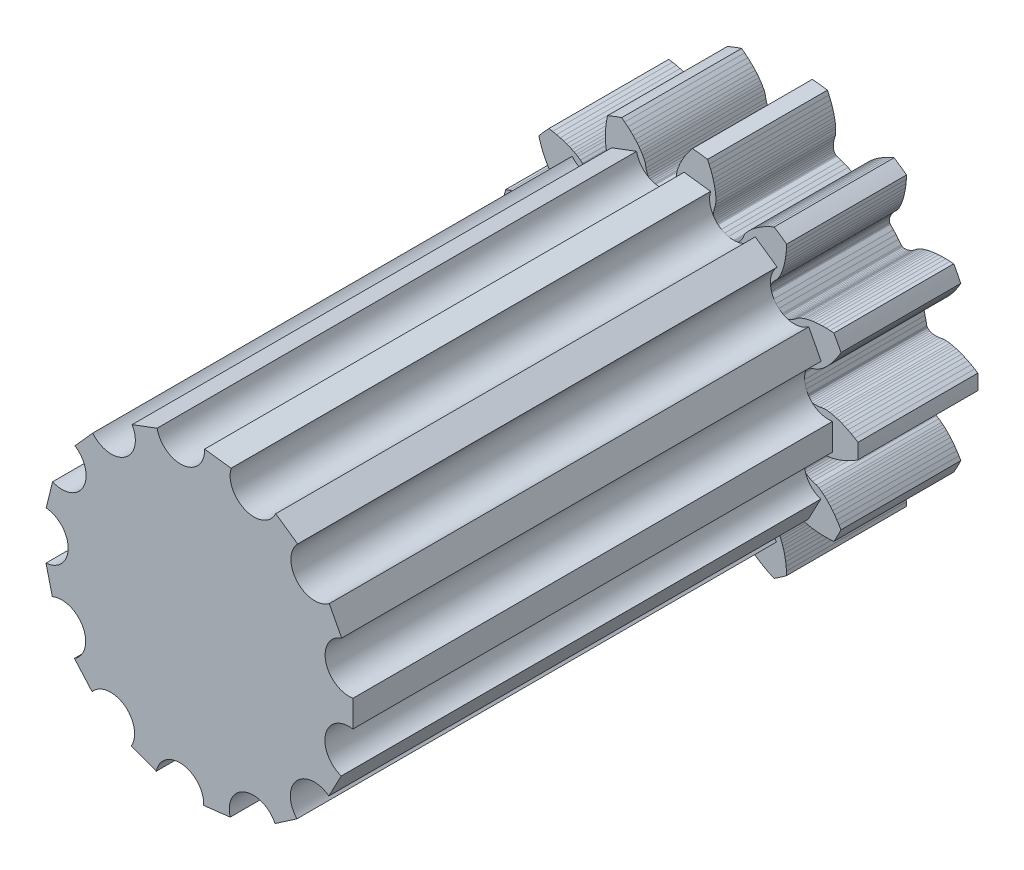
SolidWorks part; units mm, degrees
ref_plane "Front Plane" through (0, 0, 0) normal (0, 0, 1) x (1, 0, 0)
ref_plane "Top Plane" through (0, 0, 0) normal (0, 1, 0) x (1, 0, 0)
ref_plane "Right Plane" through (0, 0, 0) normal (1, 0, 0) x (0, 0, -1)
sketch "Model" plane through (0, 0, 0) normal (0, 0, 1) x (1, 0, 0)
  line L0 (13.726, -4.5793) -> (13.7795, -4.4216)
  line L1 (13.7795, -4.4216) -> (13.8362, -4.2751)
  line L2 (13.8362, -4.2751) -> (13.8946, -4.1409)
  line L3 (13.8946, -4.1409) -> (13.9531, -4.0207)
  line L4 (13.9531, -4.0207) -> (14.0126, -3.9103)
  line L5 (14.0126, -3.9103) -> (14.071, -3.8121)
  line L6 (14.071, -3.8121) -> (14.1274, -3.7258)
  line L7 (14.1274, -3.7258) -> (14.1809, -3.6508)
  line L8 (14.1809, -3.6508) -> (14.2315, -3.5859)
  line L9 (14.2315, -3.5859) -> (14.3187, -3.4872)
  line L10 (14.3187, -3.4872) -> (14.4038, -3.4082)
  line L11 (14.4038, -3.4082) -> (14.5511, -3.3203)
  line L12 (14.5511, -3.3203) -> (14.636, -3.2587)
  line L13 (14.636, -3.2587) -> (14.7072, -3.1963)
  line L14 (14.7072, -3.1963) -> (14.7648, -3.1341)
  line L15 (14.7648, -3.1341) -> (14.8089, -3.0731)
  line L16 (14.8089, -3.0731) -> (14.8397, -3.0144)
  line L17 (14.8397, -3.0144) -> (14.8576, -2.9589)
  line L18 (14.8576, -2.9589) -> (14.8629, -2.9077)
  line L19 (14.8629, -2.9077) -> (14.8609, -2.884)
  line L20 (14.8609, -2.884) -> (14.8559, -2.8617)
  line L21 (14.8559, -2.8617) -> (14.8429, -2.8311)
  line L22 (14.8429, -2.8311) -> (14.7494, -2.6711)
  line L23 (14.7494, -2.6711) -> (14.6743, -2.5327)
  line L24 (14.6743, -2.5327) -> (14.6031, -2.3923)
  line L25 (14.6031, -2.3923) -> (14.5246, -2.2245)
  line L26 (14.5246, -2.2245) -> (14.5068, -2.1964)
  line L27 (14.5068, -2.1964) -> (14.4912, -2.1796)
  line L28 (14.4912, -2.1796) -> (14.4728, -2.1645)
  line L29 (14.4728, -2.1645) -> (14.4277, -2.1397)
  line L30 (14.4277, -2.1397) -> (14.3719, -2.1229)
  line L31 (14.3719, -2.1229) -> (14.306, -2.115)
  line L32 (14.306, -2.115) -> (14.2308, -2.1166)
  line L33 (14.2308, -2.1166) -> (14.1469, -2.1287)
  line L34 (14.1469, -2.1287) -> (14.0551, -2.1518)
  line L35 (14.0551, -2.1518) -> (13.9561, -2.1867)
  line L36 (13.9561, -2.1867) -> (13.8002, -2.258)
  line L37 (13.8002, -2.258) -> (13.6868, -2.2832)
  line L38 (13.6868, -2.2832) -> (13.556, -2.2989)
  line L39 (13.556, -2.2989) -> (13.4739, -2.3036)
  line L40 (13.4739, -2.3036) -> (13.3817, -2.3051)
  line L41 (13.3817, -2.3051) -> (13.2787, -2.3025)
  line L42 (13.2787, -2.3025) -> (13.1647, -2.2947)
  line L43 (13.1647, -2.2947) -> (13.0401, -2.281)
  line L44 (13.0401, -2.281) -> (12.9079, -2.2608)
  line L45 (12.9079, -2.2608) -> (12.7642, -2.2327)
  line L46 (12.7642, -2.2327) -> (12.6115, -2.1961)
  line L47 (12.6115, -2.1961) -> (12.4513, -2.1505)
  line L48 (12.4513, -2.1505) -> (12.3003, -2.1009)
  line L49 (12.1486, -1.4856) -> (12.2592, -1.3715)
  line L50 (12.2592, -1.3715) -> (12.38, -1.2567)
  line L51 (12.38, -1.2567) -> (12.4982, -1.1533)
  line L52 (12.4982, -1.1533) -> (12.6123, -1.0616)
  line L53 (12.6123, -1.0616) -> (12.72, -0.9823)
  line L54 (12.72, -0.9823) -> (12.8239, -0.9123)
  line L55 (12.8239, -0.9123) -> (12.9213, -0.8525)
  line L56 (12.9213, -0.8525) -> (13.0113, -0.8022)
  line L57 (13.0113, -0.8022) -> (13.0936, -0.7607)
  line L58 (13.0936, -0.7607) -> (13.1685, -0.7268)
  line L59 (13.1685, -0.7268) -> (13.2916, -0.6799)
  line L60 (13.2916, -0.6799) -> (13.4037, -0.6495)
  line L61 (13.4037, -0.6495) -> (13.5749, -0.6401)
  line L62 (13.5749, -0.6401) -> (13.6788, -0.625)
  line L63 (13.6788, -0.625) -> (13.7708, -0.6029)
  line L64 (13.7708, -0.6029) -> (13.8507, -0.5745)
  line L65 (13.8507, -0.5745) -> (13.9181, -0.541)
  line L66 (13.9181, -0.541) -> (13.9727, -0.5034)
  line L67 (13.9727, -0.5034) -> (14.0143, -0.4626)
  line L68 (14.0143, -0.4626) -> (14.0427, -0.4197)
  line L69 (14.0427, -0.4197) -> (14.052, -0.3977)
  line L70 (14.052, -0.3977) -> (14.058, -0.3756)
  line L71 (14.058, -0.3756) -> (14.0607, -0.3425)
  line L72 (14.0607, -0.3425) -> (14.0523, -0.1574)
  line L73 (14.0523, -0.1574) -> (14.05, 0)
  line L74 (14.05, 0) -> (14.0523, 0.1574)
  line L75 (14.0523, 0.1574) -> (14.0607, 0.3425)
  line L76 (14.0607, 0.3425) -> (14.058, 0.3756)
  line L77 (14.058, 0.3756) -> (14.052, 0.3977)
  line L78 (14.052, 0.3977) -> (14.0427, 0.4197)
  line L79 (14.0427, 0.4197) -> (14.0143, 0.4626)
  line L80 (14.0143, 0.4626) -> (13.9727, 0.5034)
  line L81 (13.9727, 0.5034) -> (13.9181, 0.541)
  line L82 (13.9181, 0.541) -> (13.8507, 0.5745)
  line L83 (13.8507, 0.5745) -> (13.7708, 0.6029)
  line L84 (13.7708, 0.6029) -> (13.6788, 0.625)
  line L85 (13.6788, 0.625) -> (13.5749, 0.6401)
  line L86 (13.5749, 0.6401) -> (13.4037, 0.6495)
  line L87 (13.4037, 0.6495) -> (13.2916, 0.6799)
  line L88 (13.2916, 0.6799) -> (13.1685, 0.7268)
  line L89 (13.1685, 0.7268) -> (13.0936, 0.7607)
  line L90 (13.0936, 0.7607) -> (13.0113, 0.8022)
  line L91 (13.0113, 0.8022) -> (12.9213, 0.8525)
  line L92 (12.9213, 0.8525) -> (12.8239, 0.9123)
  line L93 (12.8239, 0.9123) -> (12.72, 0.9823)
  line L94 (12.72, 0.9823) -> (12.6123, 1.0616)
  line L95 (12.6123, 1.0616) -> (12.4982, 1.1533)
  line L96 (12.4982, 1.1533) -> (12.38, 1.2567)
  line L97 (12.38, 1.2567) -> (12.2592, 1.3715)
  line L98 (12.2592, 1.3715) -> (12.1486, 1.4856)
  line L99 (12.3003, 2.1009) -> (12.4513, 2.1505)
  line L100 (12.4513, 2.1505) -> (12.6115, 2.1961)
  line L101 (12.6115, 2.1961) -> (12.7642, 2.2327)
  line L102 (12.7642, 2.2327) -> (12.9079, 2.2608)
  line L103 (12.9079, 2.2608) -> (13.0401, 2.281)
  line L104 (13.0401, 2.281) -> (13.1647, 2.2947)
  line L105 (13.1647, 2.2947) -> (13.2787, 2.3025)
  line L106 (13.2787, 2.3025) -> (13.3817, 2.3051)
  line L107 (13.3817, 2.3051) -> (13.4739, 2.3036)
  line L108 (13.4739, 2.3036) -> (13.556, 2.2989)
  line L109 (13.556, 2.2989) -> (13.6868, 2.2832)
  line L110 (13.6868, 2.2832) -> (13.8002, 2.258)
  line L111 (13.8002, 2.258) -> (13.9561, 2.1867)
  line L112 (13.9561, 2.1867) -> (14.0551, 2.1518)
  line L113 (14.0551, 2.1518) -> (14.1469, 2.1287)
  line L114 (14.1469, 2.1287) -> (14.2308, 2.1166)
  line L115 (14.2308, 2.1166) -> (14.306, 2.115)
  line L116 (14.306, 2.115) -> (14.3719, 2.1229)
  line L117 (14.3719, 2.1229) -> (14.4277, 2.1397)
  line L118 (14.4277, 2.1397) -> (14.4728, 2.1645)
  line L119 (14.4728, 2.1645) -> (14.4912, 2.1796)
  line L120 (14.4912, 2.1796) -> (14.5068, 2.1964)
  line L121 (14.5068, 2.1964) -> (14.5246, 2.2245)
  line L122 (14.5246, 2.2245) -> (14.6031, 2.3923)
  line L123 (14.6031, 2.3923) -> (14.6743, 2.5327)
  line L124 (14.6743, 2.5327) -> (14.7494, 2.6711)
  line L125 (14.7494, 2.6711) -> (14.8429, 2.8311)
  line L126 (14.8429, 2.8311) -> (14.8559, 2.8617)
  line L127 (14.8559, 2.8617) -> (14.8609, 2.884)
  line L128 (14.8609, 2.884) -> (14.8629, 2.9077)
  line L129 (14.8629, 2.9077) -> (14.8576, 2.9589)
  line L130 (14.8576, 2.9589) -> (14.8397, 3.0144)
  line L131 (14.8397, 3.0144) -> (14.8089, 3.0731)
  line L132 (14.8089, 3.0731) -> (14.7648, 3.1341)
  line L133 (14.7648, 3.1341) -> (14.7072, 3.1963)
  line L134 (14.7072, 3.1963) -> (14.636, 3.2587)
  line L135 (14.636, 3.2587) -> (14.5511, 3.3203)
  line L136 (14.5511, 3.3203) -> (14.4038, 3.4082)
  line L137 (14.4038, 3.4082) -> (14.3187, 3.4872)
  line L138 (14.3187, 3.4872) -> (14.2315, 3.5859)
  line L139 (14.2315, 3.5859) -> (14.1809, 3.6508)
  line L140 (14.1809, 3.6508) -> (14.1274, 3.7258)
  line L141 (14.1274, 3.7258) -> (14.071, 3.8121)
  line L142 (14.071, 3.8121) -> (14.0126, 3.9103)
  line L143 (14.0126, 3.9103) -> (13.9531, 4.0207)
  line L144 (13.9531, 4.0207) -> (13.8946, 4.1409)
  line L145 (13.8946, 4.1409) -> (13.8362, 4.2751)
  line L146 (13.8362, 4.2751) -> (13.7795, 4.4216)
  line L147 (13.7795, 4.4216) -> (13.726, 4.5793)
  line L148 (13.726, 4.5793) -> (13.6811, 4.7318)
  line L149 (14.1013, 5.2061) -> (14.2581, 5.1799)
  line L150 (14.2581, 5.1799) -> (14.4212, 5.1458)
  line L151 (14.4212, 5.1458) -> (14.5734, 5.1072)
  line L152 (14.5734, 5.1072) -> (14.7136, 5.0654)
  line L153 (14.7136, 5.0654) -> (14.8401, 5.0218)
  line L154 (14.8401, 5.0218) -> (14.9568, 4.9761)
  line L155 (14.9568, 4.9761) -> (15.0613, 4.9299)
  line L156 (15.0613, 4.9299) -> (15.1538, 4.8844)
  line L157 (15.1538, 4.8844) -> (15.2347, 4.8402)
  line L158 (15.2347, 4.8402) -> (15.3052, 4.7979)
  line L159 (15.3052, 4.7979) -> (15.4137, 4.7232)
  line L160 (15.4137, 4.7232) -> (15.5024, 4.6482)
  line L161 (15.5024, 4.6482) -> (15.6074, 4.5126)
  line L162 (15.6074, 4.5126) -> (15.6788, 4.4357)
  line L163 (15.6788, 4.4357) -> (15.7493, 4.3726)
  line L164 (15.7493, 4.3726) -> (15.818, 4.3229)
  line L165 (15.818, 4.3229) -> (15.8838, 4.2865)
  line L166 (15.8838, 4.2865) -> (15.9458, 4.2629)
  line L167 (15.9458, 4.2629) -> (16.0031, 4.2519)
  line L168 (16.0031, 4.2519) -> (16.0545, 4.2529)
  line L169 (16.0545, 4.2529) -> (16.0779, 4.2577)
  line L170 (16.0779, 4.2577) -> (16.0994, 4.2653)
  line L171 (16.0994, 4.2653) -> (16.1282, 4.2819)
  line L172 (16.1282, 4.2819) -> (16.2758, 4.394)
  line L173 (16.2758, 4.394) -> (16.404, 4.4853)
  line L174 (16.404, 4.4853) -> (16.5349, 4.5728)
  line L175 (16.5349, 4.5728) -> (16.692, 4.671)
  line L176 (16.692, 4.671) -> (16.7177, 4.6921)
  line L177 (16.7177, 4.6921) -> (16.7325, 4.7095)
  line L178 (16.7325, 4.7095) -> (16.7453, 4.7296)
  line L179 (16.7453, 4.7296) -> (16.7645, 4.7774)
  line L180 (16.7645, 4.7774) -> (16.7744, 4.8349)
  line L181 (16.7744, 4.8349) -> (16.7744, 4.9012)
  line L182 (16.7744, 4.9012) -> (16.7637, 4.9757)
  line L183 (16.7637, 4.9757) -> (16.7416, 5.0575)
  line L184 (16.7416, 5.0575) -> (16.7076, 5.1459)
  line L185 (16.7076, 5.1459) -> (16.661, 5.2399)
  line L186 (16.661, 5.2399) -> (16.5714, 5.3861)
  line L187 (16.5714, 5.3861) -> (16.5328, 5.4957)
  line L188 (16.5328, 5.4957) -> (16.5014, 5.6236)
  line L189 (16.5014, 5.6236) -> (16.4868, 5.7045)
  line L190 (16.4868, 5.7045) -> (16.4742, 5.7958)
  line L191 (16.4742, 5.7958) -> (16.4644, 5.8985)
  line L192 (16.4644, 5.8985) -> (16.4584, 6.0125)
  line L193 (16.4584, 6.0125) -> (16.457, 6.1379)
  line L194 (16.457, 6.1379) -> (16.4611, 6.2715)
  line L195 (16.4611, 6.2715) -> (16.4717, 6.4175)
  line L196 (16.4717, 6.4175) -> (16.4896, 6.5735)
  line L197 (16.4896, 6.5735) -> (16.5155, 6.7381)
  line L198 (16.5155, 6.7381) -> (16.5466, 6.894)
  line L199 (17.1391, 7.1187) -> (17.2657, 7.0226)
  line L200 (17.2657, 7.0226) -> (17.3943, 6.9166)
  line L201 (17.3943, 6.9166) -> (17.5111, 6.8117)
  line L202 (17.5111, 6.8117) -> (17.6159, 6.7095)
  line L203 (17.6159, 6.7095) -> (17.7076, 6.6122)
  line L204 (17.7076, 6.6122) -> (17.7897, 6.5174)
  line L205 (17.7897, 6.5174) -> (17.8608, 6.428)
  line L206 (17.8608, 6.428) -> (17.9215, 6.3447)
  line L207 (17.9215, 6.3447) -> (17.9727, 6.268)
  line L208 (17.9727, 6.268) -> (18.0154, 6.1977)
  line L209 (18.0154, 6.1977) -> (18.0767, 6.0812)
  line L210 (18.0767, 6.0812) -> (18.1204, 5.9736)
  line L211 (18.1204, 5.9736) -> (18.1504, 5.8047)
  line L212 (18.1504, 5.8047) -> (18.1778, 5.7035)
  line L213 (18.1778, 5.7035) -> (18.211, 5.6148)
  line L214 (18.211, 5.6148) -> (18.2487, 5.5389)
  line L215 (18.2487, 5.5389) -> (18.2901, 5.476)
  line L216 (18.2901, 5.476) -> (18.334, 5.4264)
  line L217 (18.334, 5.4264) -> (18.3796, 5.39)
  line L218 (18.3796, 5.39) -> (18.4256, 5.3669)
  line L219 (18.4256, 5.3669) -> (18.4485, 5.3603)
  line L220 (18.4485, 5.3603) -> (18.4711, 5.3571)
  line L221 (18.4711, 5.3571) -> (18.5043, 5.3584)
  line L222 (18.5043, 5.3584) -> (18.6871, 5.389)
  line L223 (18.6871, 5.389) -> (18.8431, 5.4103)
  line L224 (18.8431, 5.4103) -> (18.9996, 5.427)
  line L225 (18.9996, 5.427) -> (19.1844, 5.4409)
  line L226 (19.1844, 5.4409) -> (19.2169, 5.4476)
  line L227 (19.2169, 5.4476) -> (19.2381, 5.4562)
  line L228 (19.2381, 5.4562) -> (19.2588, 5.4681)
  line L229 (19.2588, 5.4681) -> (19.298, 5.5015)
  line L230 (19.298, 5.5015) -> (19.3335, 5.5477)
  line L231 (19.3335, 5.5477) -> (19.3643, 5.6064)
  line L232 (19.3643, 5.6064) -> (19.3894, 5.6774)
  line L233 (19.3894, 5.6774) -> (19.4079, 5.7601)
  line L234 (19.4079, 5.7601) -> (19.4188, 5.8541)
  line L235 (19.4188, 5.8541) -> (19.4213, 5.9591)
  line L236 (19.4213, 5.9591) -> (19.4099, 6.1301)
  line L237 (19.4099, 6.1301) -> (19.4266, 6.2451)
  line L238 (19.4266, 6.2451) -> (19.4583, 6.3729)
  line L239 (19.4583, 6.3729) -> (19.4829, 6.4514)
  line L240 (19.4829, 6.4514) -> (19.5142, 6.5381)
  line L241 (19.5142, 6.5381) -> (19.5533, 6.6335)
  line L242 (19.5533, 6.6335) -> (19.6009, 6.7374)
  line L243 (19.6009, 6.7374) -> (19.6579, 6.849)
  line L244 (19.6579, 6.849) -> (19.7237, 6.9654)
  line L245 (19.7237, 6.9654) -> (19.8009, 7.0898)
  line L246 (19.8009, 7.0898) -> (19.8893, 7.2196)
  line L247 (19.8893, 7.2196) -> (19.9887, 7.3533)
  line L248 (19.9887, 7.3533) -> (20.0887, 7.4768)
  line L249 (20.7178, 7.4004) -> (20.7852, 7.2566)
  line L250 (20.7852, 7.2566) -> (20.8498, 7.1029)
  line L251 (20.8498, 7.1029) -> (20.9045, 6.9558)
  line L252 (20.9045, 6.9558) -> (20.9498, 6.8165)
  line L253 (20.9498, 6.8165) -> (20.9857, 6.6878)
  line L254 (20.9857, 6.6878) -> (21.0144, 6.5657)
  line L255 (21.0144, 6.5657) -> (21.0358, 6.4535)
  line L256 (21.0358, 6.4535) -> (21.0508, 6.3515)
  line L257 (21.0508, 6.3515) -> (21.0605, 6.2598)
  line L258 (21.0605, 6.2598) -> (21.0656, 6.1778)
  line L259 (21.0656, 6.1778) -> (21.0658, 6.0461)
  line L260 (21.0658, 6.0461) -> (21.0545, 5.9305)
  line L261 (21.0545, 5.9305) -> (21.0026, 5.7671)
  line L262 (21.0026, 5.7671) -> (20.9798, 5.6646)
  line L263 (20.9798, 5.6646) -> (20.9679, 5.5707)
  line L264 (20.9679, 5.5707) -> (20.9661, 5.4859)
  line L265 (20.9661, 5.4859) -> (20.9735, 5.411)
  line L266 (20.9735, 5.411) -> (20.9893, 5.3466)
  line L267 (20.9893, 5.3466) -> (21.0127, 5.2933)
  line L268 (21.0127, 5.2933) -> (21.0428, 5.2514)
  line L269 (21.0428, 5.2514) -> (21.06, 5.235)
  line L270 (21.06, 5.235) -> (21.0785, 5.2216)
  line L271 (21.0785, 5.2216) -> (21.1085, 5.2073)
  line L272 (21.1085, 5.2073) -> (21.2846, 5.1495)
  line L273 (21.2846, 5.1495) -> (21.4326, 5.0958)
  line L274 (21.4326, 5.0958) -> (21.579, 5.0379)
  line L275 (21.579, 5.0379) -> (21.7491, 4.9644)
  line L276 (21.7491, 4.9644) -> (21.781, 4.9552)
  line L277 (21.781, 4.9552) -> (21.8038, 4.9529)
  line L278 (21.8038, 4.9529) -> (21.8276, 4.9538)
  line L279 (21.8276, 4.9538) -> (21.8778, 4.9652)
  line L280 (21.8778, 4.9652) -> (21.9307, 4.9896)
  line L281 (21.9307, 4.9896) -> (21.9853, 5.0273)
  line L282 (21.9853, 5.0273) -> (22.0405, 5.0785)
  line L283 (22.0405, 5.0785) -> (22.0953, 5.1431)
  line L284 (22.0953, 5.1431) -> (22.1487, 5.2213)
  line L285 (22.1487, 5.2213) -> (22.1996, 5.3131)
  line L286 (22.1996, 5.3131) -> (22.2691, 5.4698)
  line L287 (22.2691, 5.4698) -> (22.3373, 5.5639)
  line L288 (22.3373, 5.5639) -> (22.4247, 5.6623)
  line L289 (22.4247, 5.6623) -> (22.483, 5.7203)
  line L290 (22.483, 5.7203) -> (22.551, 5.7826)
  line L291 (22.551, 5.7826) -> (22.6299, 5.8489)
  line L292 (22.6299, 5.8489) -> (22.7204, 5.9187)
  line L293 (22.7204, 5.9187) -> (22.8227, 5.9911)
  line L294 (22.8227, 5.9911) -> (22.9351, 6.0636)
  line L295 (22.9351, 6.0636) -> (23.0612, 6.1378)
  line L296 (23.0612, 6.1378) -> (23.1998, 6.2117)
  line L297 (23.1998, 6.2117) -> (23.35, 6.2839)
  line L298 (23.35, 6.2839) -> (23.4959, 6.3468)
  line L299 (24.0174, 5.9868) -> (24.0103, 5.8281)
  line L300 (24.0103, 5.8281) -> (23.9961, 5.6621)
  line L301 (23.9961, 5.6621) -> (23.9762, 5.5063)
  line L302 (23.9762, 5.5063) -> (23.9515, 5.362)
  line L303 (23.9515, 5.362) -> (23.9235, 5.2313)
  line L304 (23.9235, 5.2313) -> (23.8922, 5.1099)
  line L305 (23.8922, 5.1099) -> (23.859, 5.0006)
  line L306 (23.859, 5.0006) -> (23.8249, 4.9033)
  line L307 (23.8249, 4.9033) -> (23.7908, 4.8176)
  line L308 (23.7908, 4.8176) -> (23.7573, 4.7425)
  line L309 (23.7573, 4.7425) -> (23.6962, 4.6259)
  line L310 (23.6962, 4.6259) -> (23.6324, 4.5288)
  line L311 (23.6324, 4.5288) -> (23.5105, 4.4082)
  line L312 (23.5105, 4.4082) -> (23.4428, 4.3281)
  line L313 (23.4428, 4.3281) -> (23.3886, 4.2504)
  line L314 (23.3886, 4.2504) -> (23.3476, 4.1762)
  line L315 (23.3476, 4.1762) -> (23.3194, 4.1065)
  line L316 (23.3194, 4.1065) -> (23.3035, 4.0421)
  line L317 (23.3035, 4.0421) -> (23.2994, 3.984)
  line L318 (23.2994, 3.984) -> (23.3065, 3.933)
  line L319 (23.3065, 3.933) -> (23.3141, 3.9104)
  line L320 (23.3141, 3.9104) -> (23.3243, 3.8899)
  line L321 (23.3243, 3.8899) -> (23.3442, 3.8633)
  line L322 (23.3442, 3.8633) -> (23.4733, 3.7303)
  line L323 (23.4733, 3.7303) -> (23.5794, 3.614)
  line L324 (23.5794, 3.614) -> (23.6821, 3.4947)
  line L325 (23.6821, 3.4947) -> (23.7985, 3.3505)
  line L326 (23.7985, 3.3505) -> (23.8225, 3.3276)
  line L327 (23.8225, 3.3276) -> (23.8416, 3.315)
  line L328 (23.8416, 3.315) -> (23.8631, 3.3047)
  line L329 (23.8631, 3.3047) -> (23.9129, 3.2915)
  line L330 (23.9129, 3.2915) -> (23.9711, 3.2885)
  line L331 (23.9711, 3.2885) -> (24.0369, 3.2965)
  line L332 (24.0369, 3.2965) -> (24.1095, 3.3161)
  line L333 (24.1095, 3.3161) -> (24.1881, 3.3479)
  line L334 (24.1881, 3.3479) -> (24.2717, 3.3924)
  line L335 (24.2717, 3.3924) -> (24.3595, 3.4499)
  line L336 (24.3595, 3.4499) -> (24.4938, 3.5564)
  line L337 (24.4938, 3.5564) -> (24.5979, 3.608)
  line L338 (24.5979, 3.608) -> (24.7211, 3.6546)
  line L339 (24.7211, 3.6546) -> (24.7997, 3.6788)
  line L340 (24.7997, 3.6788) -> (24.8888, 3.7023)
  line L341 (24.8888, 3.7023) -> (24.9895, 3.7244)
  line L342 (24.9895, 3.7244) -> (25.1021, 3.7442)
  line L343 (25.1021, 3.7442) -> (25.2263, 3.7607)
  line L344 (25.2263, 3.7607) -> (25.3595, 3.7727)
  line L345 (25.3595, 3.7727) -> (25.5057, 3.7798)
  line L346 (25.5057, 3.7798) -> (25.6627, 3.7808)
  line L347 (25.6627, 3.7808) -> (25.8293, 3.7749)
  line L348 (25.8293, 3.7749) -> (25.9877, 3.7629)
  line L349 (26.2822, 3.2017) -> (26.2021, 3.0645)
  line L350 (26.2021, 3.0645) -> (26.1124, 2.9241)
  line L351 (26.1124, 2.9241) -> (26.0223, 2.7954)
  line L352 (26.0223, 2.7954) -> (25.9335, 2.6791)
  line L353 (25.9335, 2.6791) -> (25.8479, 2.5764)
  line L354 (25.8479, 2.5764) -> (25.7638, 2.4835)
  line L355 (25.7638, 2.4835) -> (25.6836, 2.4021)
  line L356 (25.6836, 2.4021) -> (25.6082, 2.3318)
  line L357 (25.6082, 2.3318) -> (25.5382, 2.2717)
  line L358 (25.5382, 2.2717) -> (25.4736, 2.2209)
  line L359 (25.4736, 2.2209) -> (25.3653, 2.1459)
  line L360 (25.3653, 2.1459) -> (25.2637, 2.0896)
  line L361 (25.2637, 2.0896) -> (25.0997, 2.0395)
  line L362 (25.0997, 2.0395) -> (25.0025, 2)
  line L363 (25.0025, 2) -> (24.9184, 1.9564)
  line L364 (24.9184, 1.9564) -> (24.8476, 1.9098)
  line L365 (24.8476, 1.9098) -> (24.7902, 1.8612)
  line L366 (24.7902, 1.8612) -> (24.7462, 1.8115)
  line L367 (24.7462, 1.8115) -> (24.7156, 1.762)
  line L368 (24.7156, 1.762) -> (24.6983, 1.7135)
  line L369 (24.6983, 1.7135) -> (24.6945, 1.69)
  line L370 (24.6945, 1.69) -> (24.694, 1.6671)
  line L371 (24.694, 1.6671) -> (24.6993, 1.6343)
  line L372 (24.6993, 1.6343) -> (24.7518, 1.4565)
  line L373 (24.7518, 1.4565) -> (24.7916, 1.3043)
  line L374 (24.7916, 1.3043) -> (24.8271, 1.1509)
  line L375 (24.8271, 1.1509) -> (24.8632, 0.9691)
  line L376 (24.8632, 0.9691) -> (24.8738, 0.9376)
  line L377 (24.8738, 0.9376) -> (24.8849, 0.9176)
  line L378 (24.8849, 0.9176) -> (24.8991, 0.8985)
  line L379 (24.8991, 0.8985) -> (24.937, 0.8637)
  line L380 (24.937, 0.8637) -> (24.9872, 0.834)
  line L381 (24.9872, 0.834) -> (25.0492, 0.8105)
  line L382 (25.0492, 0.8105) -> (25.1226, 0.7941)
  line L383 (25.1226, 0.7941) -> (25.207, 0.7857)
  line L384 (25.207, 0.7857) -> (25.3017, 0.7862)
  line L385 (25.3017, 0.7862) -> (25.4061, 0.7965)
  line L386 (25.4061, 0.7965) -> (25.5746, 0.8283)
  line L387 (25.5746, 0.8283) -> (25.6907, 0.8256)
  line L388 (25.6907, 0.8256) -> (25.8214, 0.8096)
  line L389 (25.8214, 0.8096) -> (25.9023, 0.7946)
  line L390 (25.9023, 0.7946) -> (25.9921, 0.7739)
  line L391 (25.9921, 0.7739) -> (26.0916, 0.7467)
  line L392 (26.0916, 0.7467) -> (26.2004, 0.7119)
  line L393 (26.2004, 0.7119) -> (26.3181, 0.6688)
  line L394 (26.3181, 0.6688) -> (26.4416, 0.6175)
  line L395 (26.4416, 0.6175) -> (26.5744, 0.5559)
  line L396 (26.5744, 0.5559) -> (26.7139, 0.4838)
  line L397 (26.7139, 0.4838) -> (26.8586, 0.4012)
  line L398 (26.8586, 0.4012) -> (26.9933, 0.3169)
  line L399 (26.9933, -0.3169) -> (26.8586, -0.4012)
  line L400 (26.8586, -0.4012) -> (26.7139, -0.4838)
  line L401 (26.7139, -0.4838) -> (26.5744, -0.5559)
  line L402 (26.5744, -0.5559) -> (26.4416, -0.6175)
  line L403 (26.4416, -0.6175) -> (26.3181, -0.6688)
  line L404 (26.3181, -0.6688) -> (26.2004, -0.7119)
  line L405 (26.2004, -0.7119) -> (26.0916, -0.7467)
  line L406 (26.0916, -0.7467) -> (25.9921, -0.7739)
  line L407 (25.9921, -0.7739) -> (25.9023, -0.7946)
  line L408 (25.9023, -0.7946) -> (25.8214, -0.8096)
  line L409 (25.8214, -0.8096) -> (25.6907, -0.8256)
  line L410 (25.6907, -0.8256) -> (25.5746, -0.8283)
  line L411 (25.5746, -0.8283) -> (25.4061, -0.7965)
  line L412 (25.4061, -0.7965) -> (25.3017, -0.7862)
  line L413 (25.3017, -0.7862) -> (25.207, -0.7857)
  line L414 (25.207, -0.7857) -> (25.1226, -0.7941)
  line L415 (25.1226, -0.7941) -> (25.0492, -0.8105)
  line L416 (25.0492, -0.8105) -> (24.9872, -0.834)
  line L417 (24.9872, -0.834) -> (24.937, -0.8637)
  line L418 (24.937, -0.8637) -> (24.8991, -0.8985)
  line L419 (24.8991, -0.8985) -> (24.8849, -0.9176)
  line L420 (24.8849, -0.9176) -> (24.8738, -0.9376)
  line L421 (24.8738, -0.9376) -> (24.8632, -0.9691)
  line L422 (24.8632, -0.9691) -> (24.8271, -1.1509)
  line L423 (24.8271, -1.1509) -> (24.7916, -1.3043)
  line L424 (24.7916, -1.3043) -> (24.7518, -1.4565)
  line L425 (24.7518, -1.4565) -> (24.6993, -1.6343)
  line L426 (24.6993, -1.6343) -> (24.694, -1.6671)
  line L427 (24.694, -1.6671) -> (24.6945, -1.69)
  line L428 (24.6945, -1.69) -> (24.6983, -1.7135)
  line L429 (24.6983, -1.7135) -> (24.7156, -1.762)
  line L430 (24.7156, -1.762) -> (24.7462, -1.8115)
  line L431 (24.7462, -1.8115) -> (24.7902, -1.8612)
  line L432 (24.7902, -1.8612) -> (24.8476, -1.9098)
  line L433 (24.8476, -1.9098) -> (24.9184, -1.9564)
  line L434 (24.9184, -1.9564) -> (25.0025, -2)
  line L435 (25.0025, -2) -> (25.0997, -2.0395)
  line L436 (25.0997, -2.0395) -> (25.2637, -2.0896)
  line L437 (25.2637, -2.0896) -> (25.3653, -2.1459)
  line L438 (25.3653, -2.1459) -> (25.4736, -2.2209)
  line L439 (25.4736, -2.2209) -> (25.5382, -2.2717)
  line L440 (25.5382, -2.2717) -> (25.6082, -2.3318)
  line L441 (25.6082, -2.3318) -> (25.6836, -2.4021)
  line L442 (25.6836, -2.4021) -> (25.7638, -2.4835)
  line L443 (25.7638, -2.4835) -> (25.8479, -2.5764)
  line L444 (25.8479, -2.5764) -> (25.9335, -2.6791)
  line L445 (25.9335, -2.6791) -> (26.0223, -2.7954)
  line L446 (26.0223, -2.7954) -> (26.1124, -2.9241)
  line L447 (26.1124, -2.9241) -> (26.2021, -3.0645)
  line L448 (26.2021, -3.0645) -> (26.2822, -3.2017)
  line L449 (25.9877, -3.7629) -> (25.8293, -3.7749)
  line L450 (25.8293, -3.7749) -> (25.6627, -3.7808)
  line L451 (25.6627, -3.7808) -> (25.5057, -3.7798)
  line L452 (25.5057, -3.7798) -> (25.3595, -3.7727)
  line L453 (25.3595, -3.7727) -> (25.2263, -3.7607)
  line L454 (25.2263, -3.7607) -> (25.1021, -3.7442)
  line L455 (25.1021, -3.7442) -> (24.9895, -3.7244)
  line L456 (24.9895, -3.7244) -> (24.8888, -3.7023)
  line L457 (24.8888, -3.7023) -> (24.7997, -3.6788)
  line L458 (24.7997, -3.6788) -> (24.7211, -3.6546)
  line L459 (24.7211, -3.6546) -> (24.5979, -3.608)
  line L460 (24.5979, -3.608) -> (24.4938, -3.5564)
  line L461 (24.4938, -3.5564) -> (24.3595, -3.4499)
  line L462 (24.3595, -3.4499) -> (24.2717, -3.3924)
  line L463 (24.2717, -3.3924) -> (24.1881, -3.3479)
  line L464 (24.1881, -3.3479) -> (24.1095, -3.3161)
  line L465 (24.1095, -3.3161) -> (24.0369, -3.2965)
  line L466 (24.0369, -3.2965) -> (23.9711, -3.2885)
  line L467 (23.9711, -3.2885) -> (23.9129, -3.2915)
  line L468 (23.9129, -3.2915) -> (23.8631, -3.3047)
  line L469 (23.8631, -3.3047) -> (23.8416, -3.315)
  line L470 (23.8416, -3.315) -> (23.8225, -3.3276)
  line L471 (23.8225, -3.3276) -> (23.7985, -3.3505)
  line L472 (23.7985, -3.3505) -> (23.6821, -3.4947)
  line L473 (23.6821, -3.4947) -> (23.5794, -3.614)
  line L474 (23.5794, -3.614) -> (23.4733, -3.7303)
  line L475 (23.4733, -3.7303) -> (23.3442, -3.8633)
  line L476 (23.3442, -3.8633) -> (23.3243, -3.8899)
  line L477 (23.3243, -3.8899) -> (23.3141, -3.9104)
  line L478 (23.3141, -3.9104) -> (23.3065, -3.933)
  line L479 (23.3065, -3.933) -> (23.2994, -3.984)
  line L480 (23.2994, -3.984) -> (23.3035, -4.0421)
  line L481 (23.3035, -4.0421) -> (23.3194, -4.1065)
  line L482 (23.3194, -4.1065) -> (23.3476, -4.1762)
  line L483 (23.3476, -4.1762) -> (23.3886, -4.2504)
  line L484 (23.3886, -4.2504) -> (23.4428, -4.3281)
  line L485 (23.4428, -4.3281) -> (23.5105, -4.4082)
  line L486 (23.5105, -4.4082) -> (23.6324, -4.5288)
  line L487 (23.6324, -4.5288) -> (23.6962, -4.6259)
  line L488 (23.6962, -4.6259) -> (23.7573, -4.7425)
  line L489 (23.7573, -4.7425) -> (23.7908, -4.8176)
  line L490 (23.7908, -4.8176) -> (23.8249, -4.9033)
  line L491 (23.8249, -4.9033) -> (23.859, -5.0006)
  line L492 (23.859, -5.0006) -> (23.8922, -5.1099)
  line L493 (23.8922, -5.1099) -> (23.9235, -5.2313)
  line L494 (23.9235, -5.2313) -> (23.9515, -5.362)
  line L495 (23.9515, -5.362) -> (23.9762, -5.5063)
  line L496 (23.9762, -5.5063) -> (23.9961, -5.6621)
  line L497 (23.9961, -5.6621) -> (24.0103, -5.8281)
  line L498 (24.0103, -5.8281) -> (24.0174, -5.9868)
  line L499 (23.4959, -6.3468) -> (23.35, -6.2839)
  line L500 (23.35, -6.2839) -> (23.1998, -6.2117)
  line L501 (23.1998, -6.2117) -> (23.0612, -6.1378)
  line L502 (23.0612, -6.1378) -> (22.9351, -6.0636)
  line L503 (22.9351, -6.0636) -> (22.8227, -5.9911)
  line L504 (22.8227, -5.9911) -> (22.7204, -5.9187)
  line L505 (22.7204, -5.9187) -> (22.6299, -5.8489)
  line L506 (22.6299, -5.8489) -> (22.551, -5.7826)
  line L507 (22.551, -5.7826) -> (22.483, -5.7203)
  line L508 (22.483, -5.7203) -> (22.4247, -5.6623)
  line L509 (22.4247, -5.6623) -> (22.3373, -5.5639)
  line L510 (22.3373, -5.5639) -> (22.2691, -5.4698)
  line L511 (22.2691, -5.4698) -> (22.1996, -5.3131)
  line L512 (22.1996, -5.3131) -> (22.1487, -5.2213)
  line L513 (22.1487, -5.2213) -> (22.0953, -5.1431)
  line L514 (22.0953, -5.1431) -> (22.0405, -5.0785)
  line L515 (22.0405, -5.0785) -> (21.9853, -5.0273)
  line L516 (21.9853, -5.0273) -> (21.9307, -4.9896)
  line L517 (21.9307, -4.9896) -> (21.8778, -4.9652)
  line L518 (21.8778, -4.9652) -> (21.8276, -4.9538)
  line L519 (21.8276, -4.9538) -> (21.8038, -4.9529)
  line L520 (21.8038, -4.9529) -> (21.781, -4.9552)
  line L521 (21.781, -4.9552) -> (21.7491, -4.9644)
  line L522 (21.7491, -4.9644) -> (21.579, -5.0379)
  line L523 (21.579, -5.0379) -> (21.4326, -5.0958)
  line L524 (21.4326, -5.0958) -> (21.2846, -5.1495)
  line L525 (21.2846, -5.1495) -> (21.1085, -5.2073)
  line L526 (21.1085, -5.2073) -> (21.0785, -5.2216)
  line L527 (21.0785, -5.2216) -> (21.06, -5.235)
  line L528 (21.06, -5.235) -> (21.0428, -5.2514)
  line L529 (21.0428, -5.2514) -> (21.0127, -5.2933)
  line L530 (21.0127, -5.2933) -> (20.9893, -5.3466)
  line L531 (20.9893, -5.3466) -> (20.9735, -5.411)
  line L532 (20.9735, -5.411) -> (20.9661, -5.4859)
  line L533 (20.9661, -5.4859) -> (20.9679, -5.5707)
  line L534 (20.9679, -5.5707) -> (20.9798, -5.6646)
  line L535 (20.9798, -5.6646) -> (21.0026, -5.7671)
  line L536 (21.0026, -5.7671) -> (21.0545, -5.9305)
  line L537 (21.0545, -5.9305) -> (21.0658, -6.0461)
  line L538 (21.0658, -6.0461) -> (21.0656, -6.1778)
  line L539 (21.0656, -6.1778) -> (21.0605, -6.2598)
  line L540 (21.0605, -6.2598) -> (21.0508, -6.3515)
  line L541 (21.0508, -6.3515) -> (21.0358, -6.4535)
  line L542 (21.0358, -6.4535) -> (21.0144, -6.5657)
  line L543 (21.0144, -6.5657) -> (20.9857, -6.6878)
  line L544 (20.9857, -6.6878) -> (20.9498, -6.8165)
  line L545 (20.9498, -6.8165) -> (20.9045, -6.9558)
  line L546 (20.9045, -6.9558) -> (20.8498, -7.1029)
  line L547 (20.8498, -7.1029) -> (20.7852, -7.2566)
  line L548 (20.7852, -7.2566) -> (20.7178, -7.4004)
  line L549 (20.0887, -7.4768) -> (19.9887, -7.3533)
  line L550 (19.9887, -7.3533) -> (19.8893, -7.2196)
  line L551 (19.8893, -7.2196) -> (19.8009, -7.0898)
  line L552 (19.8009, -7.0898) -> (19.7237, -6.9654)
  line L553 (19.7237, -6.9654) -> (19.6579, -6.849)
  line L554 (19.6579, -6.849) -> (19.6009, -6.7374)
  line L555 (19.6009, -6.7374) -> (19.5533, -6.6335)
  line L556 (19.5533, -6.6335) -> (19.5142, -6.5381)
  line L557 (19.5142, -6.5381) -> (19.4829, -6.4514)
  line L558 (19.4829, -6.4514) -> (19.4583, -6.3729)
  line L559 (19.4583, -6.3729) -> (19.4266, -6.2451)
  line L560 (19.4266, -6.2451) -> (19.4099, -6.1301)
  line L561 (19.4099, -6.1301) -> (19.4213, -5.9591)
  line L562 (19.4213, -5.9591) -> (19.4188, -5.8541)
  line L563 (19.4188, -5.8541) -> (19.4079, -5.7601)
  line L564 (19.4079, -5.7601) -> (19.3894, -5.6774)
  line L565 (19.3894, -5.6774) -> (19.3643, -5.6064)
  line L566 (19.3643, -5.6064) -> (19.3335, -5.5477)
  line L567 (19.3335, -5.5477) -> (19.298, -5.5015)
  line L568 (19.298, -5.5015) -> (19.2588, -5.4681)
  line L569 (19.2588, -5.4681) -> (19.2381, -5.4562)
  line L570 (19.2381, -5.4562) -> (19.2169, -5.4476)
  line L571 (19.2169, -5.4476) -> (19.1844, -5.4409)
  line L572 (19.1844, -5.4409) -> (18.9996, -5.427)
  line L573 (18.9996, -5.427) -> (18.8431, -5.4103)
  line L574 (18.8431, -5.4103) -> (18.6871, -5.389)
  line L575 (18.6871, -5.389) -> (18.5043, -5.3584)
  line L576 (18.5043, -5.3584) -> (18.4711, -5.3571)
  line L577 (18.4711, -5.3571) -> (18.4485, -5.3603)
  line L578 (18.4485, -5.3603) -> (18.4256, -5.3669)
  line L579 (18.4256, -5.3669) -> (18.3796, -5.39)
  line L580 (18.3796, -5.39) -> (18.334, -5.4264)
  line L581 (18.334, -5.4264) -> (18.2901, -5.476)
  line L582 (18.2901, -5.476) -> (18.2487, -5.5389)
  line L583 (18.2487, -5.5389) -> (18.211, -5.6148)
  line L584 (18.211, -5.6148) -> (18.1778, -5.7035)
  line L585 (18.1778, -5.7035) -> (18.1504, -5.8047)
  line L586 (18.1504, -5.8047) -> (18.1204, -5.9736)
  line L587 (18.1204, -5.9736) -> (18.0767, -6.0812)
  line L588 (18.0767, -6.0812) -> (18.0154, -6.1977)
  line L589 (18.0154, -6.1977) -> (17.9727, -6.268)
  line L590 (17.9727, -6.268) -> (17.9215, -6.3447)
  line L591 (17.9215, -6.3447) -> (17.8608, -6.428)
  line L592 (17.8608, -6.428) -> (17.7897, -6.5174)
  line L593 (17.7897, -6.5174) -> (17.7076, -6.6122)
  line L594 (17.7076, -6.6122) -> (17.6159, -6.7095)
  line L595 (17.6159, -6.7095) -> (17.5111, -6.8117)
  line L596 (17.5111, -6.8117) -> (17.3943, -6.9166)
  line L597 (17.3943, -6.9166) -> (17.2657, -7.0226)
  line L598 (17.2657, -7.0226) -> (17.1391, -7.1187)
  line L599 (16.5466, -6.894) -> (16.5155, -6.7381)
  line L600 (16.5155, -6.7381) -> (16.4896, -6.5735)
  line L601 (16.4896, -6.5735) -> (16.4717, -6.4175)
  line L602 (16.4717, -6.4175) -> (16.4611, -6.2715)
  line L603 (16.4611, -6.2715) -> (16.457, -6.1379)
  line L604 (16.457, -6.1379) -> (16.4584, -6.0125)
  line L605 (16.4584, -6.0125) -> (16.4644, -5.8985)
  line L606 (16.4644, -5.8985) -> (16.4742, -5.7958)
  line L607 (16.4742, -5.7958) -> (16.4868, -5.7045)
  line L608 (16.4868, -5.7045) -> (16.5014, -5.6236)
  line L609 (16.5014, -5.6236) -> (16.5328, -5.4957)
  line L610 (16.5328, -5.4957) -> (16.5714, -5.3861)
  line L611 (16.5714, -5.3861) -> (16.661, -5.2399)
  line L612 (16.661, -5.2399) -> (16.7076, -5.1459)
  line L613 (16.7076, -5.1459) -> (16.7416, -5.0575)
  line L614 (16.7416, -5.0575) -> (16.7637, -4.9757)
  line L615 (16.7637, -4.9757) -> (16.7744, -4.9012)
  line L616 (16.7744, -4.9012) -> (16.7744, -4.8349)
  line L617 (16.7744, -4.8349) -> (16.7645, -4.7774)
  line L618 (16.7645, -4.7774) -> (16.7453, -4.7296)
  line L619 (16.7453, -4.7296) -> (16.7325, -4.7095)
  line L620 (16.7325, -4.7095) -> (16.7177, -4.6921)
  line L621 (16.7177, -4.6921) -> (16.692, -4.671)
  line L622 (16.692, -4.671) -> (16.5349, -4.5728)
  line L623 (16.5349, -4.5728) -> (16.404, -4.4853)
  line L624 (16.404, -4.4853) -> (16.2758, -4.394)
  line L625 (16.2758, -4.394) -> (16.1282, -4.2819)
  line L626 (16.1282, -4.2819) -> (16.0994, -4.2653)
  line L627 (16.0994, -4.2653) -> (16.0779, -4.2577)
  line L628 (16.0779, -4.2577) -> (16.0545, -4.2529)
  line L629 (16.0545, -4.2529) -> (16.0031, -4.2519)
  line L630 (16.0031, -4.2519) -> (15.9458, -4.2629)
  line L631 (15.9458, -4.2629) -> (15.8838, -4.2865)
  line L632 (15.8838, -4.2865) -> (15.818, -4.3229)
  line L633 (15.818, -4.3229) -> (15.7493, -4.3726)
  line L634 (15.7493, -4.3726) -> (15.6788, -4.4357)
  line L635 (15.6788, -4.4357) -> (15.6074, -4.5126)
  line L636 (15.6074, -4.5126) -> (15.5024, -4.6482)
  line L637 (15.5024, -4.6482) -> (15.4137, -4.7232)
  line L638 (15.4137, -4.7232) -> (15.3052, -4.7979)
  line L639 (15.3052, -4.7979) -> (15.2347, -4.8402)
  line L640 (15.2347, -4.8402) -> (15.1538, -4.8844)
  line L641 (15.1538, -4.8844) -> (15.0613, -4.9299)
  line L642 (15.0613, -4.9299) -> (14.9568, -4.9761)
  line L643 (14.9568, -4.9761) -> (14.8401, -5.0218)
  line L644 (14.8401, -5.0218) -> (14.7136, -5.0654)
  line L645 (14.7136, -5.0654) -> (14.5734, -5.1072)
  line L646 (14.5734, -5.1072) -> (14.4212, -5.1458)
  line L647 (14.4212, -5.1458) -> (14.2581, -5.1799)
  line L648 (14.2581, -5.1799) -> (14.1013, -5.2061)
  line L649 (13.6811, -4.7318) -> (13.726, -4.5793)
  circle A1 centre (19.5, 0) radius 0.75
  arc A2 (12.1486, -1.4856) -> (12.3003, -2.1009) centre (19.5, 0) ccw
  arc A3 (12.3003, 2.1009) -> (12.1486, 1.4856) centre (19.5, 0) ccw
  arc A4 (14.1013, 5.2061) -> (13.6811, 4.7318) centre (19.5, 0) ccw
  arc A5 (17.1391, 7.1187) -> (16.5466, 6.894) centre (19.5, 0) ccw
  arc A6 (20.7178, 7.4004) -> (20.0887, 7.4768) centre (19.5, 0) ccw
  arc A7 (24.0174, 5.9868) -> (23.4959, 6.3468) centre (19.5, 0) ccw
  arc A8 (26.2822, 3.2017) -> (25.9877, 3.7629) centre (19.5, 0) ccw
  arc A9 (26.9933, -0.3169) -> (26.9933, 0.3169) centre (19.5, 0) ccw
  arc A10 (25.9877, -3.7629) -> (26.2822, -3.2017) centre (19.5, 0) ccw
  arc A11 (23.4959, -6.3468) -> (24.0174, -5.9868) centre (19.5, 0) ccw
  arc A12 (20.0887, -7.4768) -> (20.7178, -7.4004) centre (19.5, 0) ccw
  arc A13 (16.5466, -6.894) -> (17.1391, -7.1187) centre (19.5, 0) ccw
  arc A14 (13.6811, -4.7318) -> (14.1013, -5.2061) centre (19.5, 0) ccw
extrude "Boss-Extrude1" add sketch "Model" along normal blind 5
sketch "Sketch2" plane through (0, 0, 5) normal (0, 0, 1) x (1, 0, 0)
  line L0 (19.7403, 6.4455) -> (20.8455, 6.3081)
  line L1 (22.7081, 5.5956) -> (23.6229, 4.9603)
  line L2 (24.9411, 3.4637) -> (25.4558, 2.4761)
  line L3 (25.9275, 0.5384) -> (25.9243, -0.5753)
  line L4 (25.4415, -2.5103) -> (24.921, -3.495)
  line L5 (23.5943, -4.9839) -> (22.6759, -5.6139)
  line L6 (20.8092, -6.3157) -> (19.7032, -6.4468)
  line L7 (17.7242, -6.2007) -> (16.684, -5.8028)
  line L8 (15.046, -4.6652) -> (14.3098, -3.8294)
  line L9 (13.3881, -2.0609) -> (13.1247, -0.9788)
  line L10 (13.1304, 1.0155) -> (13.4001, 2.0961)
  line L11 (14.3319, 3.8592) -> (15.0729, 4.6907)
  line L12 (16.7174, 5.8189) -> (17.7599, 6.2108)
  circle A1 centre (19.5, 0) radius 6.45 construction
  circle A2 centre (18.7041, -6.4007) radius 1.0001
  circle A3 centre (15.8207, -5.2977) radius 1.0001
  circle A4 centre (13.7802, -2.981) radius 1.0001
  circle A5 centre (13.05, 0.0185) radius 1.0001
  circle A6 centre (13.7975, 3.0139) radius 1.0001
  circle A7 centre (15.8513, 5.3188) radius 1.0001
  circle A8 centre (18.741, 6.4052) radius 1.0001
  circle A9 centre (21.8045, 6.0243) radius 1.0001
  circle A10 centre (24.3402, 4.2632) radius 1.0001
  circle A11 centre (25.767, 1.5256) radius 1.0001
  circle A12 centre (25.7581, -1.5616) radius 1.0001
  circle A13 centre (24.3156, -4.291) radius 1.0001
  circle A14 centre (21.7698, -6.0374) radius 1.0001
  point P35 (19.5, 0)
  point P61 (19.5, 0)
  dimension "D3" = 13
  dimension "D4" = 13
extrude "Boss-Extrude2" add sketch "Sketch2" along normal blind 20 contours A14 L5 A13 L4 A12 L3 A11 L2 A10 L1 A9 L0 A8 L12 A7 L11 A6 L10 A5 L9 A4 L8 A3 L7 A2 L6 region at (19.5, 0, 5)
